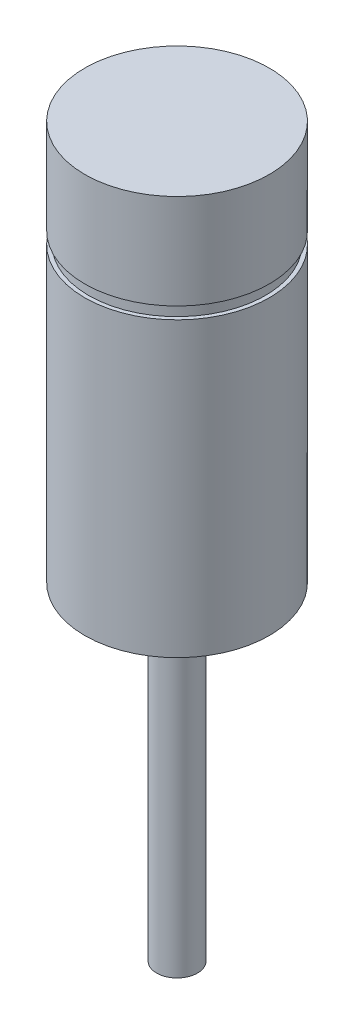
SolidWorks part; units mm, degrees
ref_plane "Front Plane" through (0, 0, 0) normal (0, 0, 1) x (1, 0, 0)
ref_plane "Top Plane" through (0, 0, 0) normal (0, 1, 0) x (1, 0, 0)
ref_plane "Right Plane" through (0, 0, 0) normal (1, 0, 0) x (0, 0, -1)
sketch "Sketch2" plane through (0, 0, 0) normal (1, 0, 0) x (0, 0, -1)
  line L0 (0, 0) -> (2, 0)
  line L1 (2, 0) -> (2, 27.94)
  line L2 (2, 27.94) -> (6.7945, 32.0802)
  line L3 (6.7945, 32.0802) -> (9.017, 32.0802)
  line L4 (9.017, 32.0802) -> (9.017, 60.6806)
  line L5 (9.017, 60.6806) -> (8.636, 60.6806)
  line L6 (8.636, 60.6806) -> (8.636, 61.849)
  line L7 (8.636, 61.849) -> (9.017, 61.849)
  line L8 (9.017, 61.849) -> (9.017, 71.12)
  line L9 (9.017, 71.12) -> (0, 71.12)
  line L10 (0, 71.12) -> (0, 0)
  dimension "D1" = 2
  dimension "D2" = 27.94
  dimension "D3" = 6.7945
  dimension "D4" = 9.017
  dimension "D5" = 4.1402
  dimension "D6" = 1.1684
  dimension "D7" = 0.381
  dimension "D8" = 9.271
  dimension "D9" = 71.12
revolve "Revolve1" add sketch "Sketch2" angle 360 about L10
